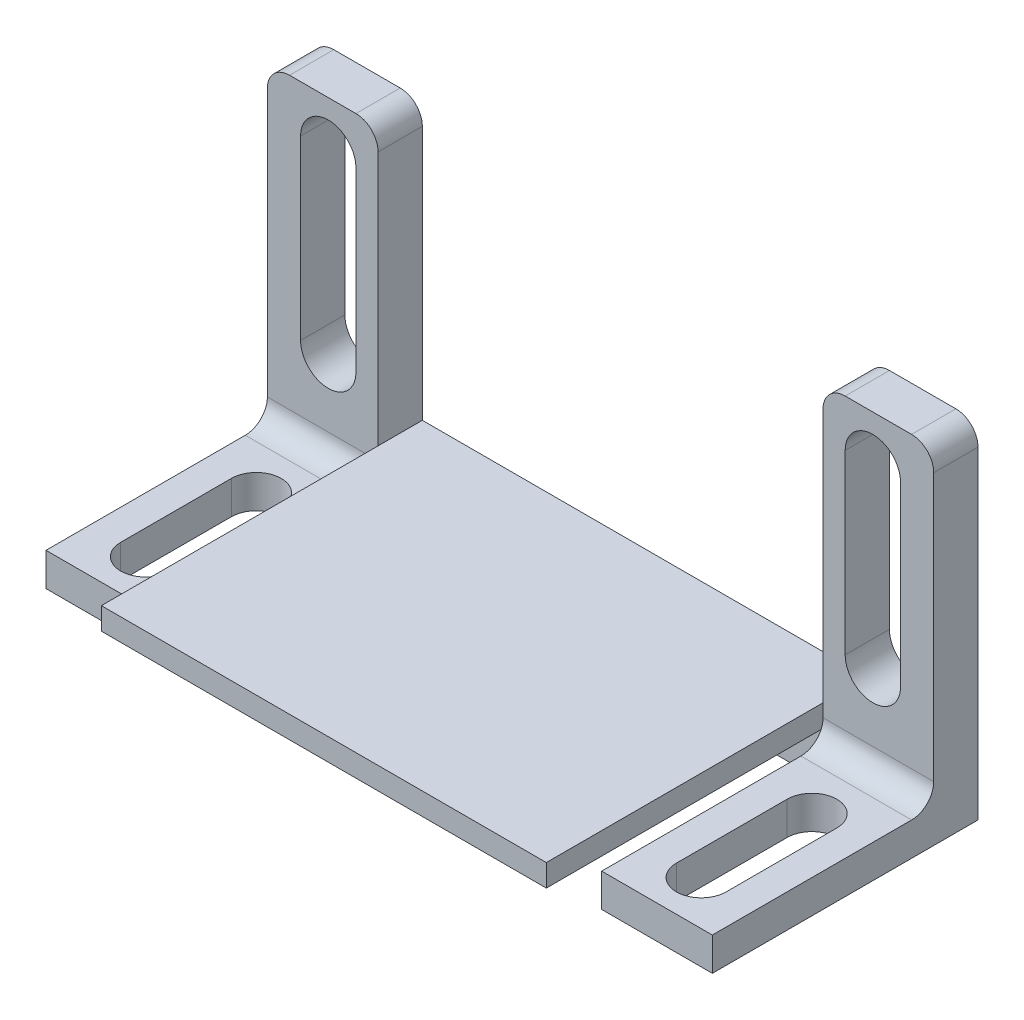
SolidWorks part; units mm, degrees
ref_plane "Front Plane" through (0, 0, 0) normal (0, 0, 1) x (1, 0, 0)
ref_plane "Top Plane" through (0, 0, 0) normal (0, 1, 0) x (1, 0, 0)
ref_plane "Right Plane" through (0, 0, 0) normal (1, 0, 0) x (0, 0, -1)
sketch "Sketch1" plane through (0, 0, 0) normal (0, 0, 1) x (1, 0, 0)
  line L0 (5.5, 20.75) -> (5.5, 4.75) construction
  line L1 (0, 0) -> (10, 0)
  line L2 (0, 0) -> (0, 25)
  line L3 (0, 25) -> (10, 25)
  line L4 (10, 0) -> (10, 25)
  line L5 (8, 20.75) -> (8, 4.75)
  line L6 (3, 20.75) -> (3, 4.75)
  line L7 (10, 0) -> (50.2, 0)
  line L8 (30.1, 0) -> (30.1, 23.7744)
  line L9 (50.2, 0) -> (50.2, 25)
  line L10 (60.2, 25) -> (50.2, 25)
  line L11 (60.2, 0) -> (60.2, 25)
  line L12 (60.2, 0) -> (50.2, 0)
  line L13 (54.7, 20.75) -> (54.7, 4.75) construction
  line L14 (52.2, 20.75) -> (52.2, 4.75)
  line L15 (57.2, 20.75) -> (57.2, 4.75)
  line L17 (0, 0) -> (60.2, 0)
  line L18 (0, 0) -> (0, -2)
  line L19 (0, -2) -> (60.2, -2)
  line L20 (60.2, 0) -> (60.2, -2)
  line L21 (10, 0) -> (50.2, 0)
  line L22 (10, 0) -> (10, -2)
  line L23 (10, -2) -> (50.2, -2)
  line L24 (50.2, 0) -> (50.2, -2)
  arc A0 (8, 20.75) -> (3, 20.75) centre (5.5, 20.75) ccw
  arc A1 (3, 4.75) -> (8, 4.75) centre (5.5, 4.75) ccw
  arc A2 (52.2, 20.75) -> (57.2, 20.75) centre (54.7, 20.75) cw
  arc A3 (57.2, 4.75) -> (52.2, 4.75) centre (54.7, 4.75) cw
  point P7 (5.5, 12.75)
  point P20 (54.7, 12.75)
  dimension "D3" = 16
  dimension "D7" = 40.2
  dimension "D1" = 4.5
  dimension "D2" = 5
  dimension "D4" = 25
  dimension "D5" = 4.75
  dimension "D6" = 10
  dimension "D8" = 2
extrude "Boss-Extrude1" add sketch "Sketch1" along normal blind 4 contours L1 L4 L3 L2 A1 L6 A0 L5 | L12 L11 L10 L9 L15 A3 L14 A2 region at (0.2693, 12.5, 0) region at (50.4693, 12.5, 0)
extrude "Boss-Extrude2" add sketch "Sketch1<3>" along normal blind 29 separate body contours L24 L7 L22 L19 region at (30.1, -1, 0)
sketch "Sketch1<3>" plane through (0, 0, 0) normal (0, 0, 1) x (1, 0, 0) same geometry as "Sketch1"
extrude "Boss-Extrude3" add sketch "Sketch1<4>" along normal blind 4 contours L22 L1 L18 L19 | L12 L24 L19 L20 region at (5, -1, 0) region at (55.2, -1, 0)
sketch "Sketch1<4>" plane through (0, 0, 0) normal (0, 0, 1) x (1, 0, 0) same geometry as "Sketch1"
fillet "Fillet2" radius 2 4 edges at (60.2, 25, 2) (50.2, 25, 2) (10, 25, 2) (0, 25, 2)
sketch "Sketch2" plane through (0, -2, 0) normal (0, -1, 0) x (1, 0, 0)
  line L12 (0, 4) -> (60.2, 4)
  line L13 (0, 4) -> (0, 0)
  line L14 (0, 0) -> (60.2, 0)
  line L15 (60.2, 4) -> (60.2, 0)
extrude "Boss-Extrude5" add sketch "Sketch2" along normal blind 4.17 contours L12 L15 L14 L13
sketch "Sketch3" plane through (0, 0, 4) normal (0, 0, 1) x (1, 0, 0)
  line L5 (30.1, -6.17) -> (30.1, -14.6788)
  line L6 (0, -6.17) -> (60.2, -6.17) construction
  line L7 (10, 0) -> (10, 25) construction
  line L8 (0, -6.17) -> (10, -6.17)
  line L9 (0, -6.17) -> (0, -3.17)
  line L10 (0, -3.17) -> (10, -3.17)
  line L11 (10, -6.17) -> (10, -3.17)
  line L12 (50.2, -6.17) -> (50.2, -3.17)
  line L13 (60.2, -3.17) -> (50.2, -3.17)
  line L14 (60.2, -6.17) -> (60.2, -3.17)
  line L15 (60.2, -6.17) -> (50.2, -6.17)
  dimension "D1" = 3
extrude "Boss-Extrude6" add sketch "Sketch3" along normal blind 20 contours L13 L12 | L10 L11 L8 L9 region at (55.2, -4.67, 4)
fillet "Fillet3" radius 2 2 edges at (55.2, -3.17, 4) (5, -3.17, 4)
sketch "Sketch4" plane through (0, -3.17, 0) normal (0, 1, 0) x (1, 0, 0)
  line L0 (5, -20) -> (5, -10) construction
  line L1 (2.75, -20) -> (2.75, -10)
  line L2 (7.25, -20) -> (7.25, -10)
  line L3 (0, -24) -> (10, -24) construction
  line L4 (0, -24) -> (0, -6) construction
  line L5 (30.1, 0) -> (30.1, -29)
  line L6 (0, 0) -> (60.2, 0) construction
  line L7 (10, -29) -> (50.2, -29) construction
  line L8 (55.2, -20) -> (55.2, -10) construction
  line L9 (57.45, -20) -> (57.45, -10)
  line L10 (52.95, -20) -> (52.95, -10)
  arc A0 (2.75, -20) -> (7.25, -20) centre (5, -20) ccw
  arc A1 (7.25, -10) -> (2.75, -10) centre (5, -10) ccw
  arc A2 (57.45, -20) -> (52.95, -20) centre (55.2, -20) cw
  arc A3 (52.95, -10) -> (57.45, -10) centre (55.2, -10) cw
  point P2 (5, -15)
  point P9 (5, -24)
  point P12 (0, -15)
  point P21 (55.2, -15)
  dimension "D1" = 4.5
  dimension "D2" = 10
extrude "Cut-Extrude1" cut sketch "Sketch4" against normal blind 15 contours L2 A1 L1 A0 | A3 L10 A2 L9 region at (5, -3.17, 15) region at (55.2, -3.17, 15)
